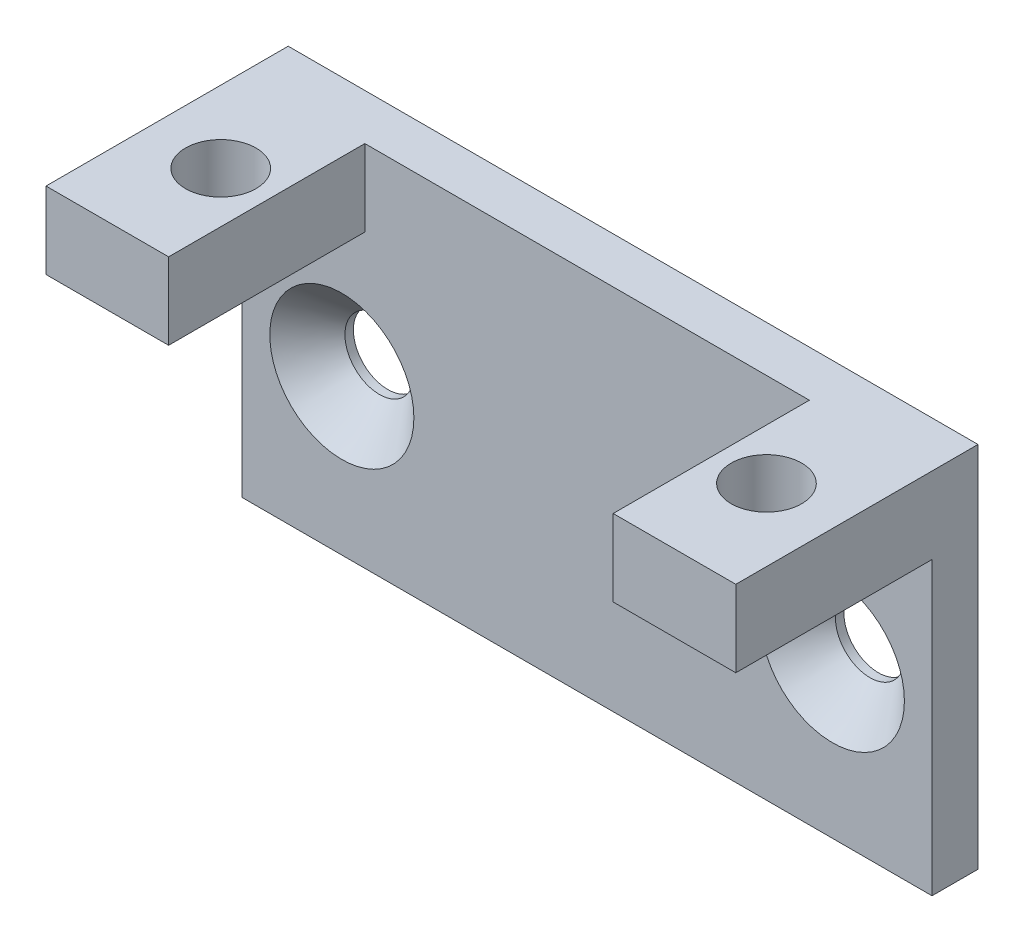
SolidWorks part; units mm, degrees
ref_plane "Face" through (0, 0, 0) normal (0, 0, 1) x (1, 0, 0)
ref_plane "Dessus" through (0, 0, 0) normal (0, 1, 0) x (1, 0, 0)
ref_plane "Droite" through (0, 0, 0) normal (1, 0, 0) x (0, 0, -1)
sketch "Esquisse1" plane through (0, 0, 0) normal (0, 0, 1) x (1, 0, 0)
  line L1 (0, 0) -> (45, 0)
  line L2 (0, 0) -> (0, 19)
  line L3 (0, 19) -> (45, 19)
  line L4 (45, 0) -> (45, 19)
  dimension "D1" = 19
  dimension "D2" = 45
extrude "Boss.-Extru.1" add sketch "Esquisse1" along normal blind 3
hole_wizard "Fraisage pour vis à tête fraisée M42" positions "Esquisse6" profile "Esquisse5" countersink size "M4" standard "Ansi Metric" end condition through all
sketch "Esquisse6" plane through (0, 0, 3) normal (0, 0, 1) x (1, 0, 0)
  line L0 (45, 0) -> (45, 19) construction
  line L2 (45, 19) -> (0, 19) construction
  point P0 (38.5, 10.1)
  dimension "D1" = 6.5
  dimension "D2" = 8.9
sketch "Esquisse5" plane through (38.5, 10.1, 3) normal (1, 0, 0) x (0, -1, 0)
  line L0 (0, 0) -> (0, 3)
  line L1 (0, 3) -> (2.25, 3)
  line L2 (2.25, 3) -> (2.25, 2.45)
  line L3 (2.25, 2.45) -> (4.7, 0)
  line L5 (4.7, 0) -> (0, 0)
  line L6 (-2.25, 2.45) -> (-4.7, 0) construction
  line L11 (0, -6.35) -> (0, 107.95) construction
  dimension "Diamètre du perçage jusqu'au prochain" = 4.5
  dimension "Profondeur du perçage jusqu'au prochain" = 3
  dimension "Diamètre du fraisage entrant" = 9.4
  dimension "Angle du fraisage entrant" = 90
pattern_linear "Répétition linéaire3" count 2 spacing 32 along (-1, 0, 0) of "Fraisage pour vis à tête fraisée M42"
ref_plane "Plan1" through (45, 19, 0) normal (-1, 0, 0) x (0, 0, 1)
sketch "Esquisse7" plane through (45, 19, 0) normal (-1, 0, 0) x (0, 0, 1)
  line L1 (0, 0) -> (15.8, 0)
  line L2 (0, 0) -> (0, 5)
  line L3 (0, 5) -> (15.8, 5)
  line L4 (15.8, 0) -> (15.8, 5)
  dimension "D1" = 5
  dimension "D2" = 15.8
extrude "Boss.-Extru.2" add sketch "Esquisse7" along normal up to vertex (45 mm away) up to point (0, 19, 3)
sketch "Esquisse8" plane through (0, 19, 0) normal (0, -1, 0) x (1, 0, 0)
  line L0 (45, 3) -> (45, 15.8) construction
  line L1 (8, 15.8) -> (37, 15.8)
  line L2 (8, 15.8) -> (8, 3)
  line L3 (8, 3) -> (37, 3)
  line L4 (37, 15.8) -> (37, 3)
  line L5 (45, 3) -> (0, 3) construction
  line L6 (0, 15.8) -> (45, 15.8) construction
  dimension "D1" = 29
  dimension "D2" = 0
  dimension "D3" = 0
  dimension "D4" = 8
extrude "Enlèv. mat.-Extru.4" cut sketch "Esquisse8" against normal blind 3
extrude "Enlèv. mat.-Extru.5" cut sketch "Esquisse8<5>" against normal through all
sketch "Esquisse8<5>" plane through (0, 19, 0) normal (0, -1, 0) x (1, 0, 0) same geometry as "Esquisse8"
sketch "Esquisse9" plane through (0, 24, 0) normal (0, 1, 0) x (1, 0, 0)
  line L0 (45, -15.8) -> (45, 0) construction
  line L2 (37, -15.8) -> (45, -15.8) construction
  circle A0 centre (40.3, -9.1) radius 2.3
  dimension "D3" = 4.6
  dimension "D1" = 4.7
  dimension "D2" = 6.7
extrude "Enlèv. mat.-Extru.6" cut sketch "Esquisse9" against normal blind 10
ref_plane "Plan2" through (22.5, 0, 0) normal (1, 0, 0) x (0, 0, -1)
mirror "Symétrie1" about plane through (22.5, 0, 0) normal (1, 0, 0) of "Enlèv. mat.-Extru.6"
